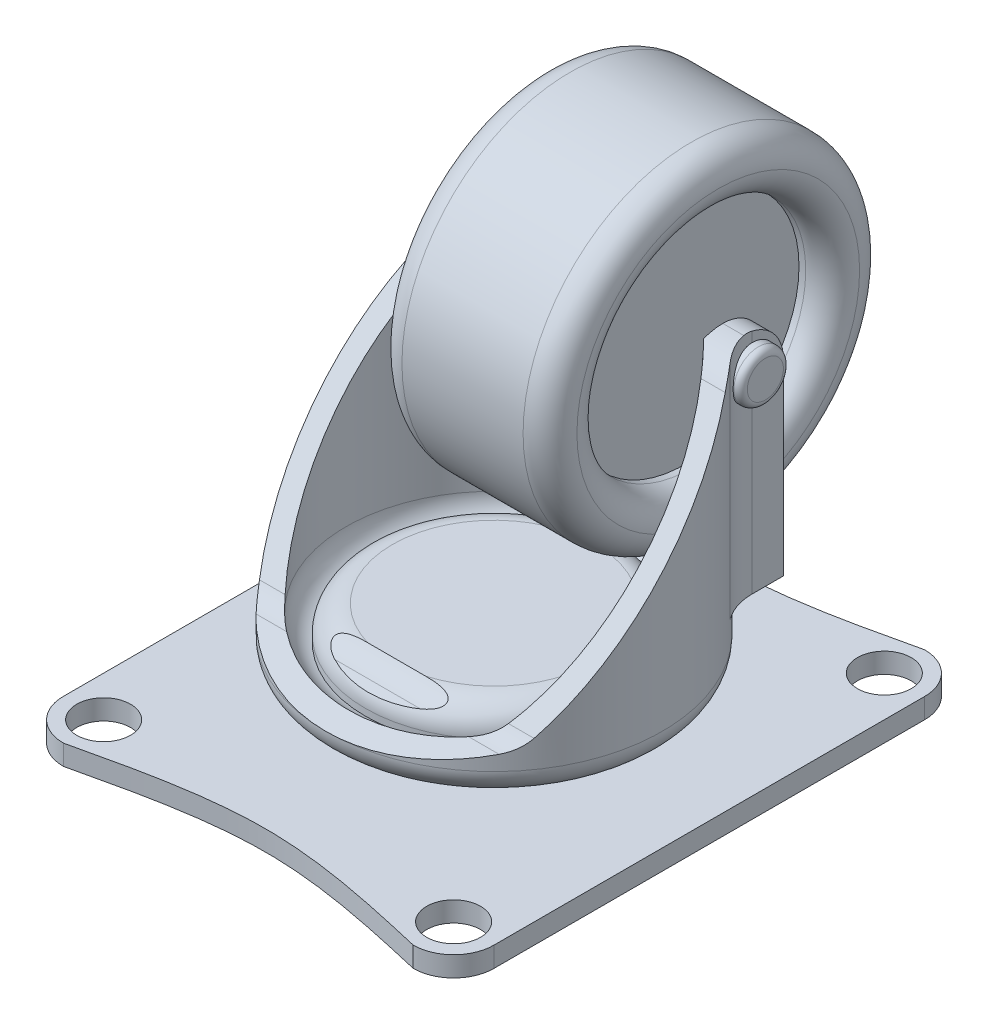
SolidWorks part; units mm, degrees
ref_plane "Front Plane" through (0, 0, 0) normal (0, 0, 1) x (1, 0, 0)
ref_plane "Top Plane" through (0, 0, 0) normal (0, 1, 0) x (1, 0, 0)
ref_plane "Right Plane" through (0, 0, 0) normal (1, 0, 0) x (0, 0, -1)
sketch "Sketch1" plane through (0, 0, 0) normal (0, 1, 0) x (1, 0, 0)
  line L2 (-25.0565, 17.1296) -> (-25.0565, 49.1296)
  line L4 (6.9435, 17.1296) -> (6.9435, 49.1296)
  arc A0 (-25.0565, 17.1296) -> (-22.0565, 14.1296) centre (-22.0565, 17.1296) ccw
  arc A1 (-22.0565, 52.1296) -> (-25.0565, 49.1296) centre (-22.0565, 49.1296) ccw
  arc A2 (3.9435, 52.1296) -> (6.9435, 49.1296) centre (3.9435, 49.1296) cw
  arc A3 (6.9435, 17.1296) -> (3.9435, 14.1296) centre (3.9435, 17.1296) cw
  circle A4 centre (-22.0565, 17.1296) radius 2
  circle A5 centre (-22.0565, 49.1296) radius 2
  circle A6 centre (3.9435, 49.1296) radius 2
  circle A7 centre (3.9435, 17.1296) radius 2
  spline S0 degree 3 poles (-22.0565, 14.1296) (-17.7231, 15.1296) (-9.0565, 17.1296) (-0.3898, 15.1296) (3.9435, 14.1296) knots 0 0 0 0 0.5 1 1 1 1
  spline S1 degree 3 poles (-22.0565, 52.1296) (-17.7231, 51.1296) (-9.0565, 49.1296) (-0.3898, 51.1296) (3.9435, 52.1296) knots 0 0 0 0 0.5 1 1 1 1
  dimension "D1" = 3
extrude "Extrude1" add sketch "Sketch1" along normal blind 1.5
sketch "Sketch2" plane through (0, 1.5, 0) normal (0, 1, 0) x (1, 0, 0)
  circle A0 centre (-9.0565, 33.1296) radius 5
extrude "Extrude2" add sketch "Sketch2" along normal blind 2
fillet "Fillet1" radius 1 1 edges at (-9.0565, 1.5, -28.1296)
fillet "Fillet2" radius 1 1 edges at (-9.0565, 3.5, -28.1296)
sketch "Sketch3" plane through (0, 3.5, 0) normal (0, 1, 0) x (1, 0, 0)
  circle A0 centre (-9.0565, 33.1296) radius 12.5
extrude "Extrude3" add sketch "Sketch3" along normal blind 4
sketch "Sketch4" plane through (0, 7.5, 0) normal (0, 1, 0) x (1, 0, 0)
  circle A0 centre (-9.0565, 33.1296) radius 11
  circle A1 centre (-9.0565, 33.1296) radius 9.5504
extrude "Cut-Extrude2" cut sketch "Sketch4" against normal blind 2.5
fillet "Fillet3" radius 2 1 edges at (-9.0565, 5, -22.1296)
fillet "Fillet4" radius 2 1 edges at (-9.0565, 3.5, -20.6296)
fillet "Fillet5" radius 2 1 edges at (-9.0565, 7.5, -23.5792)
sketch "Sketch5" plane through (0, 7.5, 0) normal (0, 1, 0) x (1, 0, 0)
  line L0 (-1.5565, 44.1296) -> (-1.5565, 41.1763)
  line L1 (-0.0565, 45.6296) -> (-18.0565, 45.6296)
  line L2 (-0.0565, 45.6296) -> (-0.0565, 41.8043)
  line L3 (-18.0565, 45.6296) -> (-18.0565, 41.8043)
  line L4 (-1.5565, 44.1296) -> (-16.5565, 44.1296)
  line L5 (-16.5565, 44.1296) -> (-16.5565, 41.1763)
  line L6 (-16.5565, 44.1296) -> (-16.5565, 41.8043) construction
  line L7 (-1.5565, 44.1296) -> (-1.5565, 41.8043) construction
  arc A0 (-18.0565, 41.8043) -> (-0.0565, 41.8043) centre (-9.0565, 33.1296) ccw
  arc A1 (-16.5565, 41.1763) -> (-1.5565, 41.1763) centre (-9.0565, 33.1296) ccw
extrude "Extrude4" add sketch "Sketch5" along normal blind 17
fillet "Fillet6" radius 4 2 edges
sketch "Sketch7" plane through (0, 24.5, 0) normal (0, 1, 0) x (1, 0, 0)
  line L0 (-0.0565, 45.6296) -> (-18.0565, 45.6296) construction
  line L1 (-1.5565, 44.1296) -> (-16.5565, 44.1296)
  line L2 (-1.5565, 44.1296) -> (-1.5565, 45.6296)
  line L3 (-1.5565, 45.6296) -> (-16.5565, 45.6296)
  line L4 (-16.5565, 44.1296) -> (-16.5565, 45.6296)
extrude "Cut-Extrude3" cut sketch "Sketch7" against normal blind 16
sketch "Sketch8" plane through (-0.0565, 0, 0) normal (1, 0, 0) x (0, 0, -1)
  line L0 (43.2908, 24.5) -> (43.2908, 7.5) construction
  circle A0 centre (43.2908, 21.8361) radius 1.349
extrude "Cut-Extrude4" cut sketch "Sketch8" against normal through all and the other way blind 16
sketch "Sketch9" plane through (-0.0565, 0, 0) normal (1, 0, 0) x (0, 0, -1)
  circle A0 centre (43.2908, 21.8361) radius 1.1699
extrude "Extrude5" add sketch "Sketch9" against normal blind 18
sketch "Sketch10" plane through (-0.0565, 0, 0) normal (1, 0, 0) x (0, 0, -1)
  circle A0 centre (43.2908, 21.8361) radius 1.8411
extrude "Extrude6" add sketch "Sketch10" along normal blind 1
sketch "Sketch11" plane through (-18.0565, 0, 0) normal (-1, 0, 0) x (0, 0, 1)
  circle A0 centre (-43.2908, 21.8361) radius 1.6545
extrude "Extrude7" add sketch "Sketch11" along normal blind 1
fillet "Fillet8" radius 0.5 1 edges at (-19.0565, 21.8361, -41.6363)
fillet "Fillet9" radius 0.5 1 edges at (0.9435, 21.8361, -45.1318)
fillet "Fillet10" radius 3 2 edges at (-0.8065, 24.5, -45.6296) (-17.3065, 24.5, -45.6296)
ref_plane "Plane1" through (-9.0565, 0, 0) normal (-1, 0, 0) x (0, 0, 1)
sketch "Sketch12" plane through (-9.0565, 0, 0) normal (-1, 0, 0) x (0, 0, 1)
  line L0 (-20.6296, 24.5) -> (-40.8275, 24.5) construction
  line L1 (-20.6296, 24.5) -> (-40.8275, 24.5)
  line L2 (-20.6296, 24.5) -> (-20.6296, 5.5)
  line L3 (-20.6296, 5.5) -> (-20.6296, 24.5) construction
  line L4 (-20.6296, 5.5) -> (-24.4835, 6.6116)
  line L5 (-25.906, 7.5142) -> (-40.8275, 24.5)
  arc A0 (-25.906, 7.5142) -> (-24.4835, 6.6116) centre (-23.6521, 9.4941) ccw
  dimension "D1" = 3
extrude "Cut-Extrude5" cut sketch "Sketch12" against normal through all and the other way through all
fillet "Fillet11" radius 4 2 edges at (-17.9095, 24.5, -40.8275) (-0.2034, 24.5, -40.8275)
sketch "Sketch13" plane through (-9.0565, 0, 0) normal (-1, 0, 0) x (0, 0, 1)
  circle A2 centre (-43.2908, 21.8361) radius 12.5
extrude "Extrude8" add sketch "Sketch13" along normal blind 6.5 and the other way blind 6.5
sketch "Sketch15" plane through (-2.5565, 0, 0) normal (1, 0, 0) x (0, 0, -1)
  circle A0 centre (43.2908, 21.8361) radius 8.5
extrude "Cut-Extrude7" cut sketch "Sketch15" against normal blind 2.5
sketch "Sketch16" plane through (-15.5565, 0, 0) normal (-1, 0, 0) x (0, 0, 1)
  circle A0 centre (-43.2908, 21.8361) radius 8.5
extrude "Cut-Extrude9" cut sketch "Sketch16" against normal blind 3
fillet "Fillet12" radius 2 2 edges at (-2.5565, 21.8361, -51.7908) (-2.5565, 21.8361, -30.7908)
fillet "Fillet13" radius 2 2 edges at (-15.5565, 21.8361, -34.7908) (-15.5565, 21.8361, -30.7908)
